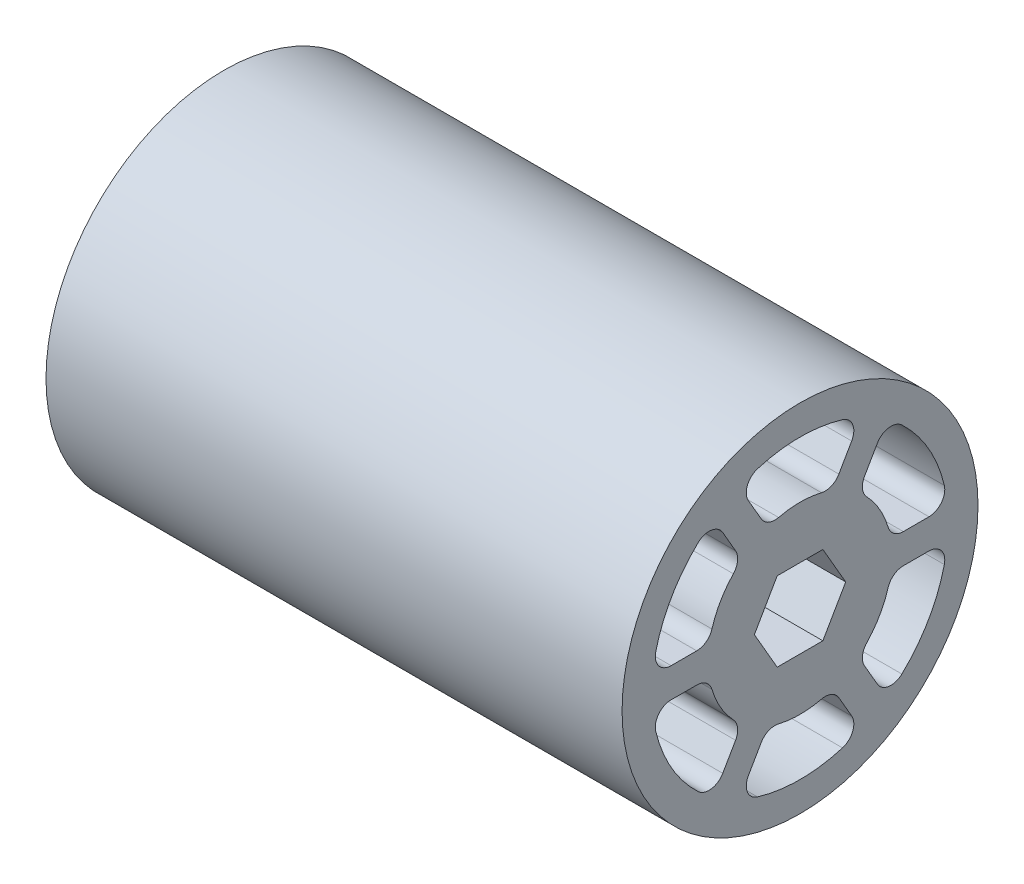
SolidWorks part; units mm, degrees
ref_plane "Alzado" through (0, 0, 0) normal (0, 0, 1) x (1, 0, 0)
ref_plane "Planta" through (0, 0, 0) normal (0, 1, 0) x (1, 0, 0)
ref_plane "Vista lateral" through (0, 0, 0) normal (1, 0, 0) x (0, 0, -1)
sketch "Croquis1" plane through (0, 0, 0) normal (1, 0, 0) x (0, 0, -1)
  line L1 (7.3323, 0) -> (3.6662, 6.35)
  line L2 (3.6662, 6.35) -> (-3.6662, 6.35)
  line L3 (-3.6662, 6.35) -> (-7.3323, 0)
  line L4 (-7.3323, 0) -> (-3.6662, -6.35)
  line L5 (-3.6662, -6.35) -> (3.6662, -6.35)
  line L6 (3.6662, -6.35) -> (7.3323, 0)
  circle A0 centre (0, 0) radius 28.575
  circle A1 centre (0, 0) radius 6.35 construction
  dimension "D1" = 57.15
  dimension "D2" = 12.7
extrude "Saliente-Extruir1" add sketch "Croquis1" along normal blind 92.5
sketch "Croquis2" plane through (92.5, 0, 0) normal (1, 0, 0) x (0, 0, -1)
  line L0 (-6.2338, 15.5507) -> (-8.2925, 19.1165)
  line L1 (6.2338, 15.5507) -> (8.2925, 19.1165)
  line L2 (16.5842, 2.3767) -> (20.7016, 2.3767)
  line L3 (10.3504, 13.174) -> (12.4091, 16.7398)
  line L4 (10.3504, -13.174) -> (12.4091, -16.7398)
  line L5 (16.5842, -2.3767) -> (20.7016, -2.3767)
  line L6 (-6.2338, -15.5507) -> (-8.2925, -19.1165)
  line L7 (6.2338, -15.5507) -> (8.2925, -19.1165)
  line L8 (-16.5842, -2.3767) -> (-20.7016, -2.3767)
  line L9 (-10.3504, -13.174) -> (-12.4091, -16.7398)
  line L10 (-10.3504, 13.174) -> (-12.4091, 16.7398)
  line L11 (-16.5842, 2.3767) -> (-20.7016, 2.3767)
  arc A0 (-3.4421, 14.351) -> (3.4421, 14.351) centre (0, 0.0082) cw
  arc A1 (-6.8204, 22.8196) -> (6.8204, 22.8196) centre (0, 0.016) cw
  arc A2 (-8.2925, 19.1165) -> (-6.8204, 22.8196) centre (-6.0925, 20.3861) cw
  arc A3 (8.2925, 19.1165) -> (6.8204, 22.8196) centre (6.0925, 20.3861) ccw
  arc A4 (3.4421, 14.351) -> (6.2338, 15.5507) centre (4.0346, 16.82) ccw
  arc A5 (-6.2338, 15.5507) -> (-3.4421, 14.351) centre (-4.0342, 16.821) ccw
  arc A6 (20.7016, 2.3767) -> (23.1725, 5.5032) centre (20.7011, 4.9167) ccw
  arc A7 (16.3521, 17.3164) -> (23.1725, 5.5032) centre (0.0139, 0.008) cw
  arc A8 (12.4091, 16.7398) -> (16.3521, 17.3164) centre (14.6086, 15.4693) cw
  arc A9 (10.3504, 13.174) -> (10.7073, 10.1564) centre (12.5503, 11.9042) ccw
  arc A10 (10.7073, 10.1564) -> (14.1493, 4.1945) centre (0.0071, 0.0041) cw
  arc A11 (14.1493, 4.1945) -> (16.5842, 2.3767) centre (16.5839, 4.9159) ccw
  arc A12 (12.4091, -16.7398) -> (16.3521, -17.3164) centre (14.6086, -15.4693) ccw
  arc A13 (23.1725, -5.5032) -> (16.3521, -17.3164) centre (0.0139, -0.008) cw
  arc A14 (20.7016, -2.3767) -> (23.1725, -5.5032) centre (20.7011, -4.9167) cw
  arc A15 (16.5842, -2.3767) -> (14.1493, -4.1945) centre (16.5845, -4.9167) ccw
  arc A16 (14.1493, -4.1945) -> (10.7073, -10.1564) centre (0.0071, -0.0041) cw
  arc A17 (10.7073, -10.1564) -> (10.3504, -13.174) centre (12.5493, -11.9041) ccw
  arc A18 (-8.2925, -19.1165) -> (-6.8204, -22.8196) centre (-6.0925, -20.3861) ccw
  arc A19 (6.8204, -22.8196) -> (-6.8204, -22.8196) centre (0, -0.016) cw
  arc A20 (8.2925, -19.1165) -> (6.8204, -22.8196) centre (6.0925, -20.3861) cw
  arc A21 (6.2338, -15.5507) -> (3.4421, -14.351) centre (4.0342, -16.821) ccw
  arc A22 (3.4421, -14.351) -> (-3.4421, -14.351) centre (0, -0.0082) cw
  arc A23 (-3.4421, -14.351) -> (-6.2338, -15.5507) centre (-4.0346, -16.82) ccw
  arc A24 (-20.7016, -2.3767) -> (-23.1725, -5.5032) centre (-20.7011, -4.9167) ccw
  arc A25 (-16.3521, -17.3164) -> (-23.1725, -5.5032) centre (-0.0139, -0.008) cw
  arc A26 (-12.4091, -16.7398) -> (-16.3521, -17.3164) centre (-14.6086, -15.4693) cw
  arc A27 (-10.3504, -13.174) -> (-10.7073, -10.1564) centre (-12.5503, -11.9042) ccw
  arc A28 (-10.7073, -10.1564) -> (-14.1493, -4.1945) centre (-0.0071, -0.0041) cw
  arc A29 (-14.1493, -4.1945) -> (-16.5842, -2.3767) centre (-16.5839, -4.9159) ccw
  arc A30 (-12.4091, 16.7398) -> (-16.3521, 17.3164) centre (-14.6086, 15.4693) ccw
  arc A31 (-23.1725, 5.5032) -> (-16.3521, 17.3164) centre (-0.0139, 0.008) cw
  arc A32 (-20.7016, 2.3767) -> (-23.1725, 5.5032) centre (-20.7011, 4.9167) cw
  arc A33 (-16.5842, 2.3767) -> (-14.1493, 4.1945) centre (-16.5845, 4.9167) ccw
  arc A34 (-14.1493, 4.1945) -> (-10.7073, 10.1564) centre (-0.0071, 0.0041) cw
  arc A35 (-10.7073, 10.1564) -> (-10.3504, 13.174) centre (-12.5493, 11.9041) ccw
  dimension "D1" = 2.54
  dimension "D2" = 2.54
  dimension "D3" = 14.75
  dimension "D4" = 6
extrude "Cortar-Extruir1" cut sketch "Croquis2" against normal through all
